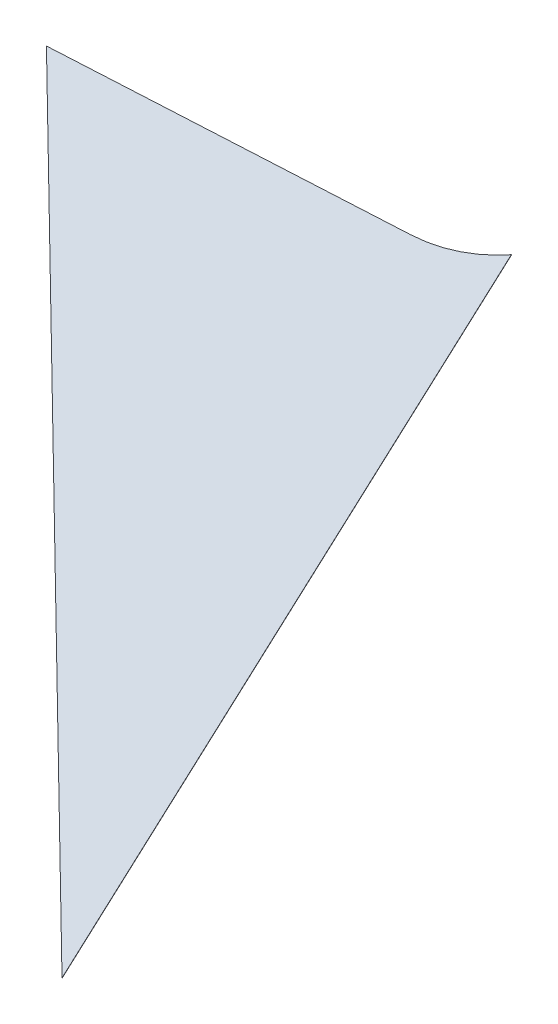
SolidWorks part; units mm, degrees
ref_plane "Front Plane" through (0, 0, 0) normal (0, 0, 1) x (1, 0, 0)
ref_plane "Top Plane" through (0, 0, 0) normal (0, 1, 0) x (1, 0, 0)
ref_plane "Right Plane" through (0, 0, 0) normal (1, 0, 0) x (0, 0, -1)
sketch "Tube Reference" plane through (-105.7197, -348.5538, -780.5289) normal (0.0456, -0.7729, -0.6329) x (0.9985, 0.0553, 0.0043)
  line L0 (-198.1328, 35.7795) -> (198.1328, 35.7795) construction
  line L1 (235, 27.0247) -> (235, 656.8278) construction
  line L2 (-198.1328, 35.7795) -> (198.1328, 35.7795)
  line L3 (235, 27.0247) -> (235, 656.8278)
  ellipse E0 centre (198.1328, -46.2165) end of major axis (280.1328, -46.2165) minor radius 81.996 (263.9946, 2.6301) -> (198.1328, 35.7795) ccw construction
  ellipse E1 centre (198.1328, -46.2165) end of major axis (280.1328, -46.2165) minor radius 81.996 (263.9946, 2.6301) -> (198.1328, 35.7795) ccw
sketch "Sketch2" plane through (-105.7197, -348.5538, -780.5289) normal (0.0456, -0.7729, -0.6329) x (0.9985, 0.0553, 0.0043)
  line L0 (-198.1328, 35.7795) -> (198.1328, 35.7795) construction
  line L1 (235, 27.0247) -> (235, 656.8278) construction
  line L2 (40.5227, 35.7795) -> (198.1328, 35.7795)
  line L3 (235, 27.0247) -> (235, 287.1081)
  line L4 (235, 27.0247) -> (235, 656.8278) construction
  line L5 (235, 287.1081) -> (40.5227, 35.7795)
  ellipse E0 centre (198.1328, -46.2165) end of major axis (280.1328, -46.2165) minor radius 81.996 (263.9946, 2.6301) -> (198.1328, 35.7795) ccw construction
  ellipse E1 centre (198.1328, -46.2165) end of major axis (280.1328, -46.2165) minor radius 81.996 (235, 27.0247) -> (198.1328, 35.7795) ccw
extrude "Boss-Extrude1" add sketch "Sketch2" along normal mid plane 0.1524
sketch "Sketch3" plane through (-105.7197, -348.5538, -780.5289) normal (0.0456, -0.7729, -0.6329) x (0.9985, 0.0553, 0.0043)
  point P0 (206.4576, 154.3059)
